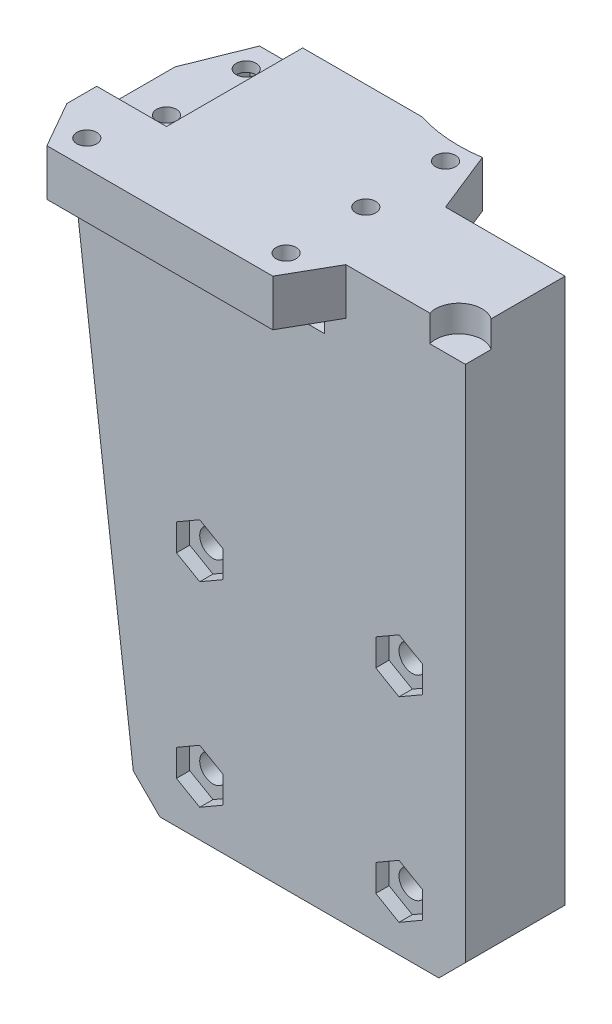
SolidWorks part; units mm, degrees
ref_plane "Front Plane" through (0, 0, 0) normal (0, 0, 1) x (1, 0, 0)
ref_plane "Top Plane" through (0, 0, 0) normal (0, 1, 0) x (1, 0, 0)
ref_plane "Right Plane" through (0, 0, 0) normal (1, 0, 0) x (0, 0, -1)
sketch "Sketch1" plane through (0, 0, 0) normal (0, 0, 1) x (1, 0, 0)
  line L1 (-25, -35) -> (25, -35)
  line L2 (-25, -35) -> (-25, 35)
  line L3 (-25, 35) -> (25, 35)
  line L4 (25, -35) -> (25, 35)
  line L5 (-25, -35) -> (25, 35) construction
  line L6 (-25, 35) -> (25, -35) construction
  point P0 (0, 0)
  dimension "D1" = 50
  dimension "D2" = 70
extrude "Boss-Extrude1" add sketch "Sketch1" along normal blind 15
sketch "Sketch2" plane through (0, 0, 15) normal (0, 0, 1) x (1, 0, 0)
  line L2 (17, -27) -> (17, 3)
  line L3 (13, 3) -> (13, -27)
  line L4 (17, -27) -> (17, 3)
  line L5 (13, 3) -> (13, -27)
  line L6 (-13, -27) -> (-13, 3)
  line L7 (-17, 3) -> (-17, -27)
  line L8 (-13, -27) -> (-13, 3)
  line L9 (-17, 3) -> (-17, -27)
  arc A3 (17, 3) -> (13, 3) centre (15, 3) ccw
  arc A4 (13, -27) -> (17, -27) centre (15, -27) ccw
  arc A5 (17, 3) -> (13, 3) centre (15, 3) ccw
  arc A6 (13, -27) -> (17, -27) centre (15, -27) ccw
  arc A8 (-13, 3) -> (-17, 3) centre (-15, 3) ccw
  arc A9 (-17, -27) -> (-13, -27) centre (-15, -27) ccw
  arc A10 (-13, 3) -> (-17, 3) centre (-15, 3) ccw
  arc A11 (-17, -27) -> (-13, -27) centre (-15, -27) ccw
  dimension "D1" = 0
  dimension "D2" = 0
sketch "Sketch3" plane through (0, 0, 15) normal (0, 0, 1) x (1, 0, 0)
  line L0 (-15, 5) -> (-15, -29) construction
  line L1 (15, 5) -> (15, -29) construction
  arc A0 (-13, 3) -> (-17, 3) centre (-15, 3) ccw construction
  arc A1 (-17, -27) -> (-13, -27) centre (-15, -27) ccw construction
  arc A2 (17, 3) -> (13, 3) centre (15, 3) ccw construction
  arc A3 (13, -27) -> (17, -27) centre (15, -27) ccw construction
  circle A4 centre (-15, 2.7) radius 2
  circle A5 centre (15, 2.7) radius 2
  circle A6 centre (-15, -26.7) radius 2
  circle A7 centre (15, -26.7) radius 2
  dimension "D1" = 4
  dimension "D2" = 0.3
  dimension "D3" = 0.3
extrude "Cut-Extrude1" cut sketch "Sketch3" against normal through all
sketch "Sketch4" plane through (0, 35, 0) normal (0, 1, 0) x (1, 0, 0)
  line L4 (25, 0) -> (-25, 0)
  line L5 (-25, 0) -> (-25, -15)
  line L6 (-25, -15) -> (25, -15)
  line L7 (25, -15) -> (25, 0)
  line L8 (25, 0) -> (-25, 0)
  line L9 (-25, 0) -> (-25, -15)
  line L10 (-25, -15) -> (25, -15)
  line L11 (25, -15) -> (25, 0)
  dimension "D1" = 0
extrude "Boss-Extrude2" add sketch "Sketch4" along normal blind 16
chamfer "Chamfer1" distance 4 angle 45 2 edges at (-25, -35, 7.5) (25, -35, 7.5)
sketch "Sketch5" plane through (0, 0, 15) normal (0, 0, 1) x (1, 0, 0)
  line L0 (-30.5, 51) -> (-27.5, 51) construction
  line L1 (-30.5, 51) -> (-27.5, 51) construction
  line L2 (-25, 51) -> (-35, 51)
  line L3 (-59, 51) -> (11, 51) construction
  line L4 (-35, 51) -> (-25, -31)
  line L5 (-25, -31) -> (-25, 51)
  dimension "D1" = 10
extrude "Boss-Extrude3" add sketch "Sketch5" against normal up to surface (15 mm away) up to face at (17, 2.7, 0)
sketch "Sketch6" plane through (0, 51, 0) normal (0, 1, 0) x (1, 0, 0)
  circle A2 centre (23, -14) radius 3.5
  circle A3 centre (23, -14) radius 3.5
  dimension "D1" = 2
extrude "Cut-Extrude2" cut sketch "Sketch6" against normal blind 4
sketch "Sketch7" plane through (0, 51, 0) normal (0, 1, 0) x (1, 0, 0)
  line L0 (-35, -15) -> (-31, -22)
  line L1 (-31, -22) -> (3, -22)
  line L2 (3, -22) -> (7, -15)
  line L3 (-35, -15) -> (19.6459, -15) construction
  line L4 (7, -15) -> (-35, -15)
  line L5 (-35, 0) -> (-31, 10)
  line L6 (-31, 10) -> (3, 10)
  line L7 (3, 10) -> (7, 0)
  line L8 (25, 0) -> (-35, 0) construction
  line L9 (7, 0) -> (-35, 0)
  circle A1 centre (-29, -18) radius 1.5 construction
  circle A2 centre (-29, -18) radius 1.5
  circle A3 centre (1, -18) radius 1.5 construction
  circle A4 centre (1, -18) radius 1.5
  circle A5 centre (-29, 6) radius 1.5 construction
  circle A6 centre (-29, 6) radius 1.5
  circle A7 centre (1, 6) radius 1.5 construction
  circle A8 centre (1, 6) radius 1.5
  circle A9 centre (-29, -6) radius 1.5 construction
  circle A10 centre (-29, -6) radius 1.5
  circle A11 centre (1, -6) radius 1.5 construction
  circle A12 centre (1, -6) radius 1.5
  dimension "D1" = 7
  dimension "D2" = 10
  dimension "D3" = 4
  dimension "D4" = 4
  dimension "D5" = 4
  dimension "D6" = 4
  dimension "D7" = 34
  dimension "D8" = 34
extrude "Boss-Extrude4" add sketch "Sketch7" against normal blind 7
sketch "Sketch8" plane through (0, 0, 15) normal (0, 0, 1) x (1, 0, 0)
  line L0 (-35, 51) -> (-34.1463, 44) construction
  line L1 (-35, 51) -> (-34.1463, 44)
  line L2 (-34.1463, 44) -> (-33.9097, 42.0597)
  line L3 (-34.1463, 44) -> (-25, -31) construction
  line L4 (-33.9097, 42.0597) -> (-44.5032, 47.1484)
  line L5 (-44.5032, 47.1484) -> (-41.9136, 51)
  line L6 (-41.9136, 51) -> (-35, 51)
extrude "Cut-Extrude3" cut sketch "Sketch8" against normal through all and the other way through all
extrude "Cut-Extrude4" cut sketch "Sketch7<2>" against normal blind 20 contours A10 | A12 region at (-29, 51, 6) region at (1, 51, 6)
sketch "Sketch7<2>" plane through (0, 51, 0) normal (0, 1, 0) x (1, 0, 0) same geometry as "Sketch7"
sketch "Sketch9" plane through (0, 0, 15) normal (0, 0, 1) x (1, 0, 0)
  line L0 (-27.5, 51) -> (-30.5, 51) construction
  line L1 (-27.5, 51) -> (-30.5, 51) construction
  line L2 (2.5, 51) -> (-0.5, 51) construction
  line L3 (2.5, 51) -> (-0.5, 51) construction
  line L4 (-29, 51) -> (-29, 32.5778) construction
  line L5 (1, 51) -> (1, 32.5778) construction
  line L6 (1, 32.5778) -> (-29, 32.5778) construction
  line L7 (-31, 51) -> (3, 51) construction
  line L8 (-31.8, 43) -> (-26.2, 43)
  line L9 (-31.8, 43) -> (-31.8, 40.4)
  line L10 (-31.8, 40.4) -> (-26.2, 40.4)
  line L11 (-26.2, 43) -> (-26.2, 40.4)
  line L12 (-31.8, 43) -> (-26.2, 40.4) construction
  line L13 (-31.8, 40.4) -> (-26.2, 43) construction
  line L14 (-1.8, 43) -> (3.8, 43)
  line L15 (-1.8, 43) -> (-1.8, 40.4)
  line L16 (-1.8, 40.4) -> (3.8, 40.4)
  line L17 (3.8, 43) -> (3.8, 40.4)
  line L18 (-1.8, 43) -> (3.8, 40.4) construction
  line L19 (-1.8, 40.4) -> (3.8, 43) construction
  point P8 (-29, 41.7)
  point P13 (1, 41.7)
  dimension "D1" = 2.6
  dimension "D2" = 5.6
  dimension "D3" = 8
extrude "Cut-Extrude5" cut sketch "Sketch9" against normal through all
sketch "Sketch10" plane through (0, 51, 0) normal (0, 1, 0) x (1, 0, 0)
  line L0 (3, 10) -> (-31, 10) construction
  line L1 (-24.5, 10) -> (-35, 10)
  line L2 (-24.5, 10) -> (-24.5, -10.5)
  line L3 (-24.5, -10.5) -> (-35, -10.5)
  line L4 (-35, 10) -> (-35, -10.5)
  line L5 (-35, 0) -> (-35, -15) construction
  circle A0 centre (-29, 6) radius 1.5 construction
  circle A1 centre (-29, -6) radius 1.5 construction
  dimension "D2" = 3
  dimension "D1" = 3
extrude "Cut-Extrude6" cut sketch "Sketch10" against normal blind 3
sketch "Sketch11" plane through (0, 44, 0) normal (0, -1, 0) x (1, 0, 0)
  line L0 (-31, -10) -> (-34.1463, -2.1341) construction
  line L1 (-30.9994, -8.5409) -> (-27.7992, -9.0019)
  line L2 (-27.7992, -9.0019) -> (-25.7999, -6.4611)
  line L3 (-25.7999, -6.4611) -> (-27.0006, -3.4591)
  line L4 (-27.0006, -3.4591) -> (-30.2008, -2.9981)
  line L5 (-30.2008, -2.9981) -> (-32.2001, -5.5389)
  line L6 (-32.2001, -5.5389) -> (-30.9994, -8.5409)
  line L7 (2.6166, -8.8) -> (4.2332, -6)
  line L8 (4.2332, -6) -> (2.6166, -3.2)
  line L9 (2.6166, -3.2) -> (-0.6166, -3.2)
  line L10 (-0.6166, -3.2) -> (-2.2332, -6)
  line L11 (-2.2332, -6) -> (-0.6166, -8.8)
  line L12 (-0.6166, -8.8) -> (2.6166, -8.8)
  line L14 (3, 22) -> (7, 15) construction
  line L15 (-32.2331, 17.9856) -> (-30.6041, 15.1928)
  line L16 (-30.6041, 15.1928) -> (-27.371, 15.2072)
  line L17 (-27.371, 15.2072) -> (-25.7669, 18.0144)
  line L18 (-25.7669, 18.0144) -> (-27.3959, 20.8072)
  line L19 (-27.3959, 20.8072) -> (-30.629, 20.7928)
  line L20 (-30.629, 20.7928) -> (-32.2331, 17.9856)
  line L21 (2.629, 20.7928) -> (-0.6041, 20.8072)
  line L22 (-0.6041, 20.8072) -> (-2.2331, 18.0144)
  line L23 (-2.2331, 18.0144) -> (-0.629, 15.2072)
  line L24 (-0.629, 15.2072) -> (2.6041, 15.1928)
  line L25 (2.6041, 15.1928) -> (4.2331, 17.9856)
  line L26 (4.2331, 17.9856) -> (2.629, 20.7928)
  line L27 (-34.1463, 16.4939) -> (-31, 22) construction
  line L28 (3, -10) -> (-31, -10) construction
  circle A0 centre (-29, -6) radius 2.8 construction
  circle A1 centre (1, -6) radius 2.8 construction
  circle A2 centre (-29, 18) radius 2.8 construction
  circle A3 centre (1, 18) radius 2.8 construction
  dimension "D1" = 5.6
  dimension "D3" = 5.6
  dimension "D2" = 0.5425
extrude "Cut-Extrude7" cut sketch "Sketch11" against normal blind 2.5
sketch "Sketch12" plane through (0, 0, 0) normal (0, 0, -1) x (-1, 0, 0)
  line L1 (-15, -1.3415) -> (-11.5, 0.6793)
  line L2 (-11.5, 0.6793) -> (-11.5, 4.7207)
  line L3 (-11.5, 4.7207) -> (-15, 6.7415)
  line L4 (-15, 6.7415) -> (-18.5, 4.7207)
  line L5 (-18.5, 4.7207) -> (-18.5, 0.6793)
  line L6 (-18.5, 0.6793) -> (-15, -1.3415)
  line L7 (-15, -30.7415) -> (-11.5, -28.7207)
  line L8 (-11.5, -28.7207) -> (-11.5, -24.6793)
  line L9 (-11.5, -24.6793) -> (-15, -22.6585)
  line L10 (-15, -22.6585) -> (-18.5, -24.6793)
  line L11 (-18.5, -24.6793) -> (-18.5, -28.7207)
  line L12 (-18.5, -28.7207) -> (-15, -30.7415)
  line L13 (15, -30.7415) -> (18.5, -28.7207)
  line L14 (18.5, -28.7207) -> (18.5, -24.6793)
  line L15 (18.5, -24.6793) -> (15, -22.6585)
  line L16 (15, -22.6585) -> (11.5, -24.6793)
  line L17 (11.5, -24.6793) -> (11.5, -28.7207)
  line L18 (11.5, -28.7207) -> (15, -30.7415)
  line L19 (15, -1.3415) -> (18.5, 0.6793)
  line L20 (18.5, 0.6793) -> (18.5, 4.7207)
  line L21 (18.5, 4.7207) -> (15, 6.7415)
  line L22 (15, 6.7415) -> (11.5, 4.7207)
  line L23 (11.5, 4.7207) -> (11.5, 0.6793)
  line L24 (11.5, 0.6793) -> (15, -1.3415)
  circle A0 centre (-15, 2.7) radius 3.5 construction
  circle A1 centre (-15, -26.7) radius 3.5 construction
  circle A2 centre (15, -26.7) radius 3.5 construction
  circle A3 centre (15, 2.7) radius 3.5 construction
  dimension "D1" = 7
sketch "Sketch13" plane through (0, 0, 15) normal (0, 0, 1) x (1, 0, 0)
  line L6 (11.5, 0.6793) -> (15, -1.3415)
  line L7 (11.5, 4.7207) -> (11.5, 0.6793)
  line L8 (15, 6.7415) -> (11.5, 4.7207)
  line L9 (18.5, 4.7207) -> (15, 6.7415)
  line L10 (18.5, 0.6793) -> (18.5, 4.7207)
  line L11 (15, -1.3415) -> (18.5, 0.6793)
  line L12 (11.5, 0.6793) -> (15, -1.3415)
  line L13 (11.5, 4.7207) -> (11.5, 0.6793)
  line L14 (15, 6.7415) -> (11.5, 4.7207)
  line L15 (18.5, 4.7207) -> (15, 6.7415)
  line L16 (18.5, 0.6793) -> (18.5, 4.7207)
  line L17 (15, -1.3415) -> (18.5, 0.6793)
  line L18 (-18.5, -28.7207) -> (-15, -30.7415)
  line L19 (-18.5, -24.6793) -> (-18.5, -28.7207)
  line L20 (-15, -22.6585) -> (-18.5, -24.6793)
  line L21 (-11.5, -24.6793) -> (-15, -22.6585)
  line L22 (-11.5, -28.7207) -> (-11.5, -24.6793)
  line L23 (-15, -30.7415) -> (-11.5, -28.7207)
  line L24 (-18.5, -28.7207) -> (-15, -30.7415)
  line L25 (-18.5, -24.6793) -> (-18.5, -28.7207)
  line L26 (-15, -22.6585) -> (-18.5, -24.6793)
  line L27 (-11.5, -24.6793) -> (-15, -22.6585)
  line L28 (-11.5, -28.7207) -> (-11.5, -24.6793)
  line L29 (-15, -30.7415) -> (-11.5, -28.7207)
  line L30 (18.5, -28.7207) -> (18.5, -24.6793)
  line L31 (18.5, -24.6793) -> (15, -22.6585)
  line L32 (15, -22.6585) -> (11.5, -24.6793)
  line L33 (11.5, -24.6793) -> (11.5, -28.7207)
  line L34 (11.5, -28.7207) -> (15, -30.7415)
  line L35 (15, -30.7415) -> (18.5, -28.7207)
  line L36 (18.5, -28.7207) -> (18.5, -24.6793)
  line L37 (18.5, -24.6793) -> (15, -22.6585)
  line L38 (15, -22.6585) -> (11.5, -24.6793)
  line L39 (11.5, -24.6793) -> (11.5, -28.7207)
  line L40 (11.5, -28.7207) -> (15, -30.7415)
  line L41 (15, -30.7415) -> (18.5, -28.7207)
  line L42 (-11.5, 4.7207) -> (-15, 6.7415)
  line L43 (-11.5, 0.6793) -> (-11.5, 4.7207)
  line L44 (-15, -1.3415) -> (-11.5, 0.6793)
  line L45 (-18.5, 0.6793) -> (-15, -1.3415)
  line L46 (-18.5, 4.7207) -> (-18.5, 0.6793)
  line L47 (-15, 6.7415) -> (-18.5, 4.7207)
  line L48 (-11.5, 4.7207) -> (-15, 6.7415)
  line L49 (-11.5, 0.6793) -> (-11.5, 4.7207)
  line L50 (-15, -1.3415) -> (-11.5, 0.6793)
  line L51 (-18.5, 0.6793) -> (-15, -1.3415)
  line L52 (-18.5, 4.7207) -> (-18.5, 0.6793)
  line L53 (-15, 6.7415) -> (-18.5, 4.7207)
  dimension "D1" = 0
  dimension "D2" = 0
  dimension "D3" = 0
  dimension "D4" = 0
extrude "Cut-Extrude8" cut sketch "Sketch13" against normal blind 2
sketch "Sketch14" plane through (0, 51, 0) normal (0, 1, 0) x (1, 0, 0)
  circle A0 centre (0, 31) radius 22
  dimension "D1" = 44
extrude "Cut-Extrude9" cut sketch "Sketch14" against normal through all
